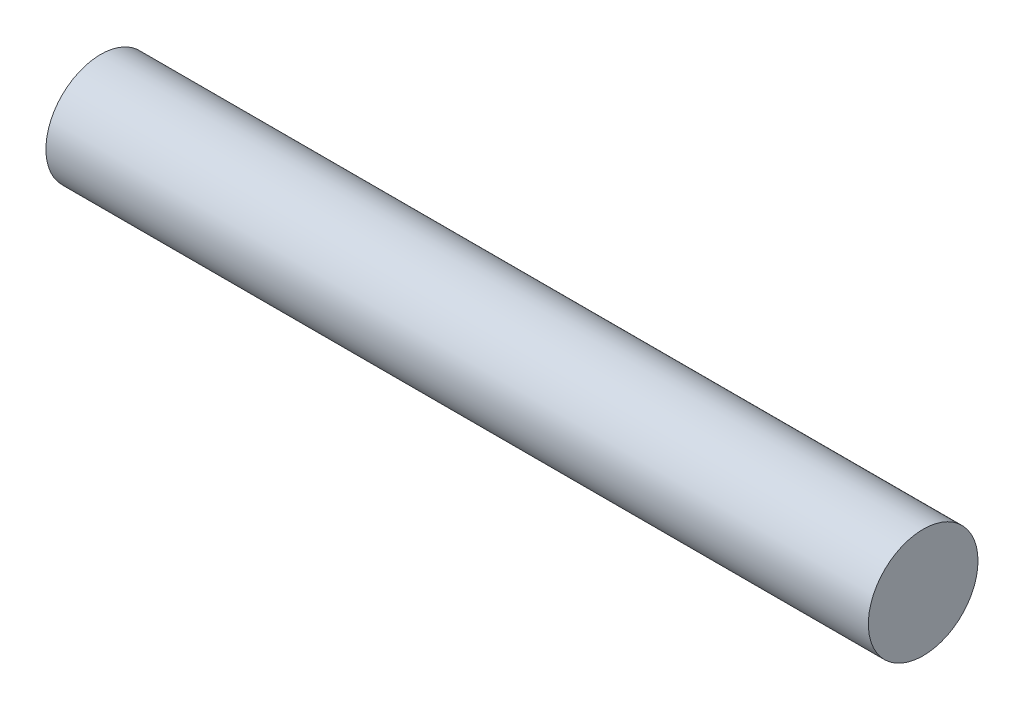
SolidWorks part; units mm, degrees
ref_plane "Plano frontal" through (0, 0, 0) normal (0, 0, 1) x (1, 0, 0)
ref_plane "Plano superior" through (0, 0, 0) normal (0, 1, 0) x (1, 0, 0)
ref_plane "Plano direito" through (0, 0, 0) normal (1, 0, 0) x (0, 0, -1)
sketch "Esboço1" plane through (0, 0, 0) normal (1, 0, 0) x (0, 0, -1)
  circle A0 centre (0, 0) radius 4
  dimension "D1" = 8
extrude "Ressalto-extrusão1" add sketch "Esboço1" along normal blind 30 and the other way blind 30
